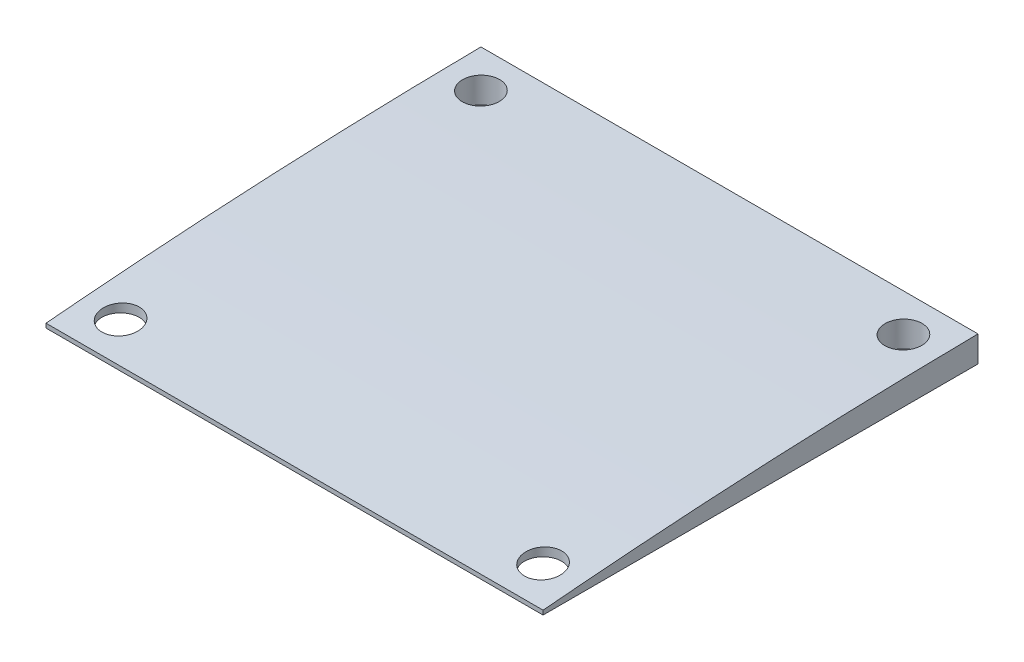
SolidWorks part; units mm, degrees
ref_plane "Спереди" through (0, 0, 0) normal (0, 0, 1) x (1, 0, 0)
ref_plane "Сверху" through (0, 0, 0) normal (0, 1, 0) x (1, 0, 0)
ref_plane "Справа" through (0, 0, 0) normal (1, 0, 0) x (0, 0, -1)
sketch "Эскиз2" plane through (0, 0, 0) normal (1, 0, 0) x (0, 0, -1)
  line L0 (17.5, -1.0477) -> (-17.5, -1.0477)
  line L1 (-17.5, -1.0477) -> (-17.5, -0.7045)
  line L2 (17.5, -1.0477) -> (17.5, 1.0477)
  spline S0 degree 2 poles (17.5, 1.0477) (-0.066, 0.8562) (-17.5, -0.7045) knots 0 0 0 0.426003 0.426003 0.426003
extrude "Бобышка-Вытянуть1" add sketch "Эскиз2" along normal blind 20 and the other way blind 20
sketch "Эскиз1" plane through (0, 0, 0) normal (0, 1, 0) x (1, 0, 0)
  circle A1 centre (-17, 14.5) radius 1.5
  circle A2 centre (17, 14.5) radius 1.5
  circle A3 centre (-17, -14.5) radius 1.5
  circle A5 centre (17, -14.5) radius 1.5
  dimension "D1" = 3
extrude "Вырез-Вытянуть1" cut sketch "Эскиз1" against normal blind 2 and the other way blind 2
